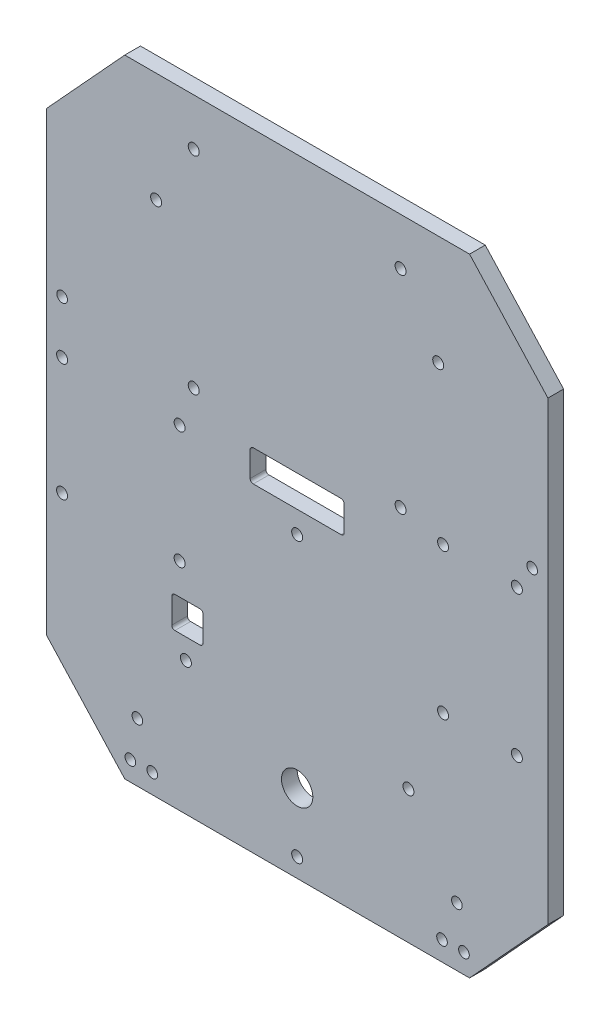
SolidWorks part; units mm, degrees
ref_plane "Plan de face" through (0, 0, 0) normal (1, 0, 0) x (0, 1, 0)
ref_plane "Plan de dessus" through (0, 0, 0) normal (0, 0, 1) x (0, 1, 0)
ref_plane "Plan de droite" through (0, 0, 0) normal (0, 1, 0) x (-1, 0, 0)
sketch "Esquisse1" plane through (0, 0, 0) normal (0, 0, 1) x (0, 1, 0)
  line L0 (0, 0) -> (-150.5414, 0) construction
  line L1 (-100, -80) -> (100, -80)
  line L2 (-100, -80) -> (-100, 80)
  line L3 (-100, 80) -> (100, 80)
  line L5 (-100, -80) -> (100, 80) construction
  line L6 (-100, 80) -> (100, -80) construction
  line L12 (-31, 38.8179) -> (-31, 42.3315) construction
  line L13 (-51, 40) -> (-41, 40)
  line L17 (-51, 40) -> (-51, 30)
  line L18 (-51, 30) -> (-41, 30)
  line L19 (-41, 40) -> (-41, 30)
  line L21 (-31.059, 37.5) -> (-30.571, 37.5) construction
  line L22 (-31, -46.5413) -> (-34.2714, -46.5413) construction
  line L28 (100, 80) -> (100, -80)
  line L30 (2, 15) -> (12, 15)
  line L31 (2, 15) -> (2, -15)
  line L32 (2, -15) -> (12, -15)
  line L33 (12, 15) -> (12, -15)
  circle A0 centre (-75, 0) radius 5
  circle A1 centre (-57.5, 35.5) radius 1.75
  circle A2 centre (-57.5, -35.5) radius 1.75
  circle A3 centre (65, 45) radius 1.75
  circle A4 centre (65, -45) radius 1.75
  circle A5 centre (-31, 37.5) radius 1.75
  circle A6 centre (-31, 75) radius 1.75
  circle A7 centre (6.5, 75) radius 1.75
  circle A8 centre (6.5, 37.5) radius 1.75
  circle A9 centre (-31, -46.5413) radius 1.75
  circle A10 centre (-31, -70.0913) radius 1.75
  circle A11 centre (15.5, -46.5413) radius 1.75
  circle A12 centre (15.5, -70.0913) radius 1.75
  circle A13 centre (-4.9993, 0) radius 1.75
  circle A16 centre (85, 33) radius 1.75
  circle A17 centre (85.0012, -33) radius 1.75
  circle A18 centre (19, 33) radius 1.75
  circle A19 centre (19.0012, -33) radius 1.75
  point P0 (0, 0)
  dimension "D3" = 10
  dimension "D9" = 3.5
  dimension "D10" = 35.5
  dimension "D11" = 17.5
  dimension "D5" = 3.5
  dimension "D6" = 45
  dimension "D7" = 15
  dimension "D16" = 37.5
  dimension "D17" = 37.5
  dimension "D18" = 37.5
  dimension "D19" = 3.5
  dimension "D20" = 3.5
  dimension "D21" = 3.5
  dimension "D22" = 3.5
  dimension "D23" = 10
  dimension "D24" = 5
  dimension "D25" = 3.5
  dimension "D26" = 3.5
  dimension "D27" = 3.5
  dimension "D28" = 3.5
  dimension "D29" = 46.5
  dimension "D30" = 46.5
  dimension "D31" = 23.55
  dimension "D32" = 23.55
  dimension "D35" = 3.5
  dimension "D36" = 3.5
  dimension "D41" = 66
  dimension "D42" = 66
  dimension "D47" = 3.5
  dimension "D48" = 3.5
  dimension "D50" = 66
  dimension "D52" = 33
  dimension "D33" = 14.9988
  dimension "D34" = 3.5
  dimension "D40" = 66
  dimension "D1" = 200
  dimension "D2" = 160
  dimension "D4" = 25
  dimension "D8" = 6.5
  dimension "D12" = 10
  dimension "D13" = 10
  dimension "D14" = 40
  dimension "D15" = 37.5
  dimension "D37" = 15
  dimension "D38" = 15
  dimension "D39" = 10
  dimension "D43" = 102
extrude "Boss.-Extru.1" add sketch "Esquisse1" along normal blind 5
fillet "Congé2" radius 1 8 edges at (-30, -51, 2.5) (-30, -41, 2.5) (-40, -41, 2.5) (-40, -51, 2.5) (15, 2, 2.5) (15, 12, 2.5) (-15, 12, 2.5) (-15, 2, 2.5)
sketch "Esquisse2" plane through (0, 0, 5) normal (0, 0, 1) x (1, 0, 0)
  line L0 (-110, 40) -> (0, 160)
  line L1 (0, 160) -> (110, 40)
  line L2 (110, 40) -> (110, -40)
  line L3 (110, -40) -> (0, -160)
  line L5 (0, -160) -> (-110, -40)
  line L6 (-110, -40) -> (-110, 40)
  line L14 (-573.5804, 598.1671) -> (-698.6982, -488.0825)
  line L15 (-80, 100) -> (-80, -100) construction
  line L16 (80, -100) -> (80, 100) construction
  line L17 (0, 70) -> (0, 33.5097) construction
  line L18 (-698.6982, -488.0825) -> (684.3, -647.3807)
  line L19 (0, 0) -> (-114.7759, 0) construction
  line L20 (684.3, -647.3807) -> (762.9047, 702.4319)
  line L21 (762.9047, 702.4319) -> (-573.5804, 598.1671)
  dimension "D1" = 160
  dimension "D2" = 160
  dimension "D3" = 40
  dimension "D4" = 40
  dimension "D5" = 40
  dimension "D6" = 40
  dimension "D7" = 110
extrude "Enlèv. mat.-Extru.1" cut sketch "Esquisse2" against normal through all
sketch "Esquisse3" plane through (0, 0, 0) normal (0, 0, 1) x (0, 1, 0)
  circle A0 centre (-94.0015, 0.004) radius 1.75
extrude "Trou cuve direction" cut sketch "Esquisse3" along normal through all
sketch "Esquisse4" plane through (0, 0, 5) normal (0, 0, 1) x (1, 0, 0)
  circle A0 centre (-50.974, -81.2615) radius 1.7
  circle A1 centre (-74.974, 23.2385) radius 1.7
  circle A2 centre (50.966, -81.2615) radius 1.7
  circle A3 centre (74.966, 23.2385) radius 1.7
  circle A4 centre (-53.224, -93.7615) radius 1.7
  circle A5 centre (46.216, -93.7615) radius 1.7
  circle A6 centre (-46.224, -93.7615) radius 1.7
  circle A7 centre (53.216, -93.7615) radius 1.7
extrude "Trous batteries et pieds" cut sketch "Esquisse4" against normal through all
